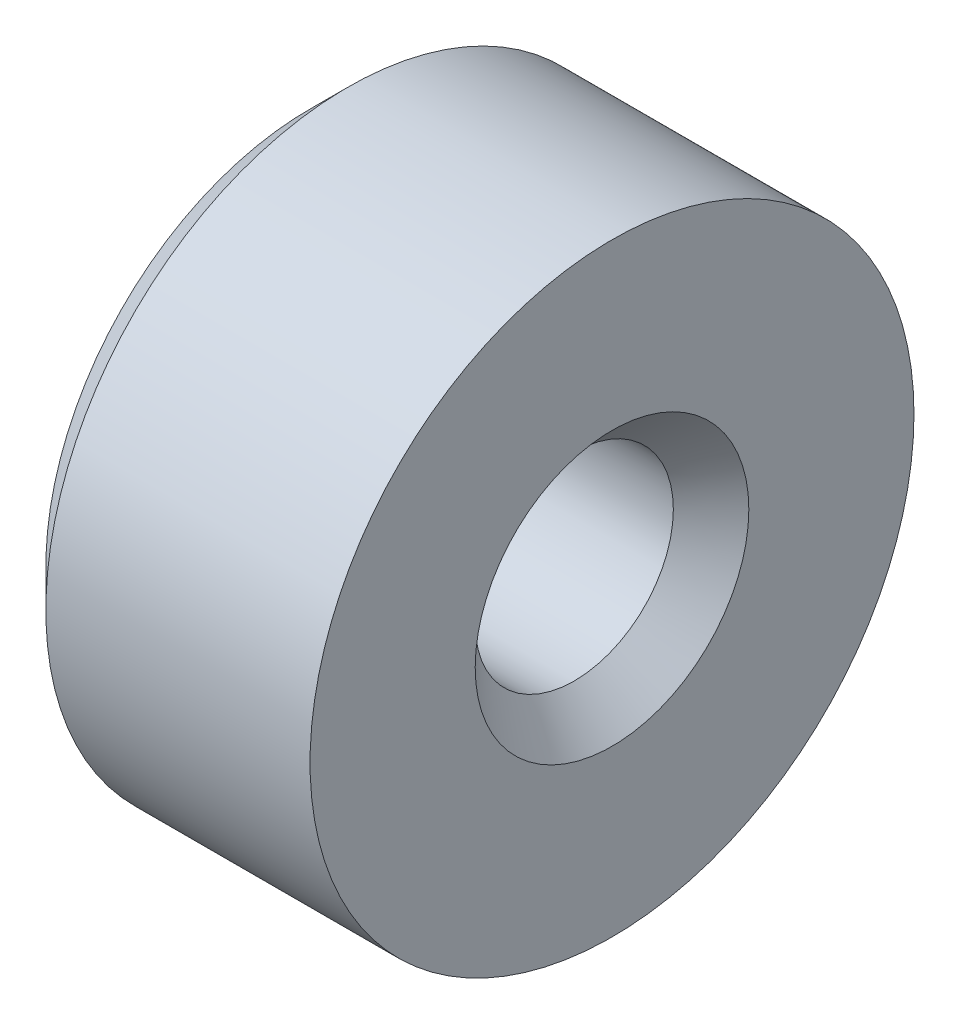
SolidWorks part; units mm, degrees
ref_plane "Vehicle Ground Plane" through (0, 0, 0) normal (0, 0, 1) x (1, 0, 0)
ref_plane "Vehicle Centreline Plane" through (0, 0, 0) normal (0, 1, 0) x (1, 0, 0)
ref_plane "Front Roll Hoop Plane" through (0, 0, 0) normal (1, 0, 0) x (0, 0, -1)
ref_axis "X-Axis" through (-1.5, 0, 0) along (1, 0, 0)
ref_axis "Y-Axis" through (0, 4.1104, 0) along (0, -1, 0)
ref_axis "Z-Axis" through (0, 0, -1.225) along (0, 0, 1)
sketch "Sketch1" plane through (0, 0, 0) normal (1, 0, 0) x (0, 0, -1)
  circle A0 centre (0, 0) radius 2.625
  circle A1 centre (0, 0) radius 8
  dimension "D1" = 5.25
  dimension "D2" = 16
extrude "Boss-Extrude1" add sketch "Sketch1" along normal blind 8
chamfer "Chamfer2" distance 1 angle 45 2 edges at (8, 0, -2.625) (0, 0, -2.625)
chamfer "Chamfer3" distance 1 angle 45 1 edges at (0, 0, -8)
